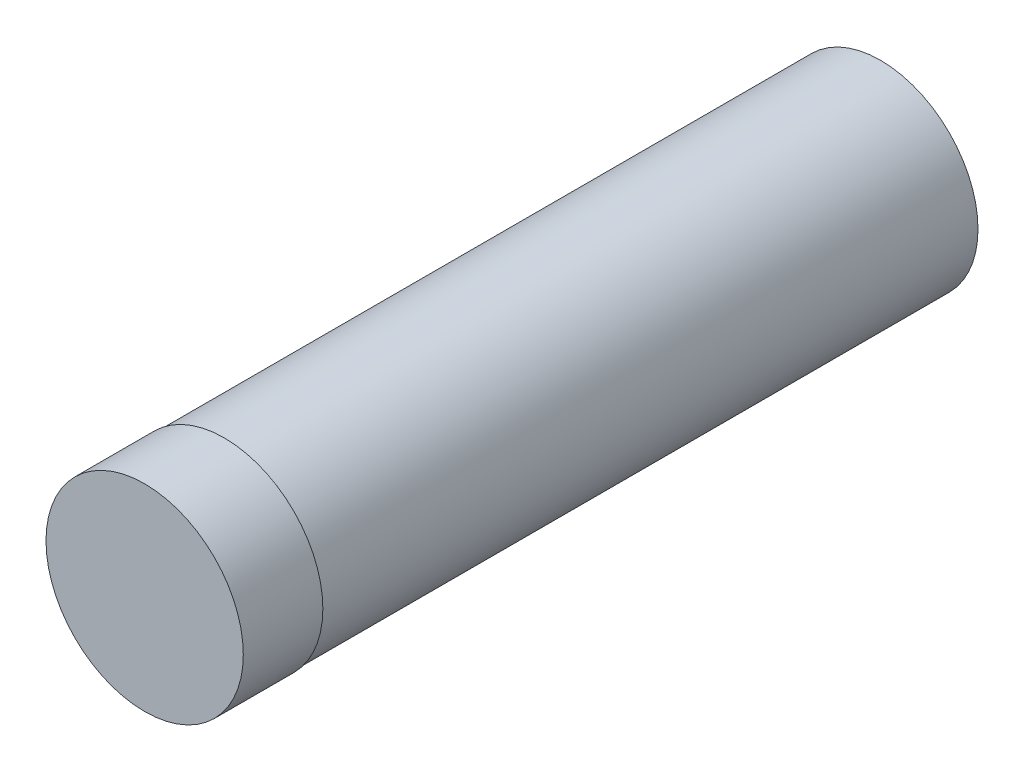
SolidWorks part; units mm, degrees
ref_plane "Front Plane" through (0, 0, 0) normal (0, 0, 1) x (1, 0, 0)
ref_plane "Top Plane" through (0, 0, 0) normal (0, 1, 0) x (1, 0, 0)
ref_plane "Right Plane" through (0, 0, 0) normal (1, 0, 0) x (0, 0, -1)
sketch "Sketch1" plane through (0, 0, 0) normal (0, 0, 1) x (1, 0, 0)
  circle A0 centre (0, 0) radius 2.45
  dimension "D1" = 4.9
extrude "Boss-Extrude1" add sketch "Sketch1" along normal mid plane 18.5
sketch "Sketch2" plane through (0, 0, 0) normal (0, 0, 1) x (1, 0, 0)
  circle A0 centre (0, 0) radius 2.5 construction
  dimension "D1" = 5
sketch "Sketch3" plane through (0, 0, 9.25) normal (0, 0, 1) x (1, 0, 0)
  circle A0 centre (0, 0) radius 2.48
  dimension "D1" = 4.96
extrude "Boss-Extrude2" add sketch "Sketch3" against normal blind 2
